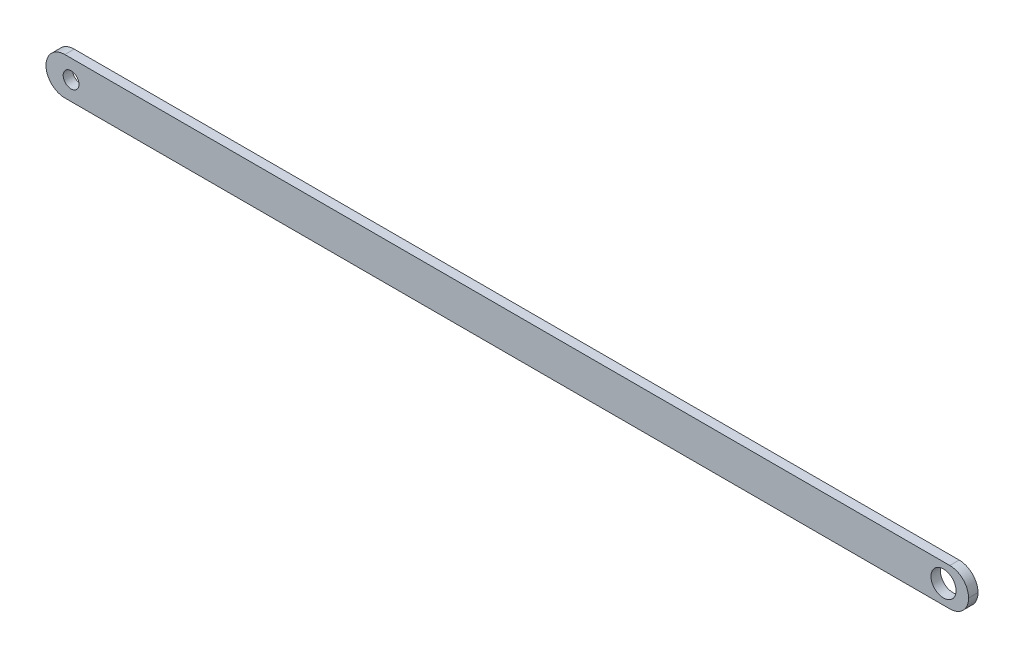
SolidWorks part; units mm, degrees
ref_plane "Front Plane" through (0, 0, 0) normal (0, 0, 1) x (1, 0, 0)
ref_plane "Top Plane" through (0, 0, 0) normal (0, 1, 0) x (1, 0, 0)
ref_plane "Right Plane" through (0, 0, 0) normal (1, 0, 0) x (0, 0, -1)
sketch "Sketch2" plane through (0, 0, 0) normal (0, 0, 1) x (1, 0, 0)
  line L1 (120.4296, 289.7111) -> (587.5796, 289.7111)
  line L2 (120.4296, 289.7111) -> (120.4296, 308.7611)
  line L3 (120.4296, 308.7611) -> (587.5796, 308.7611)
  line L4 (587.5796, 289.7111) -> (587.5796, 308.7611)
  circle A0 centre (133.1296, 299.2361) radius 4
  circle A1 centre (574.8796, 299.2361) radius 6.35
  dimension "D3" = 12.7
  dimension "D4" = 8
  dimension "D1" = 441.75
  dimension "D2" = 19.05
  dimension "D5" = 12.7
  dimension "D6" = 9.525
extrude "Boss-Extrude1" add sketch "Sketch2" along normal blind 4.7625
fillet "Fillet1" radius 9.525 4 edges at (587.5796, 308.7611, 2.3813) (587.5796, 289.7111, 2.3813) (120.4296, 289.7111, 2.3813) (120.4296, 308.7611, 2.3813)
